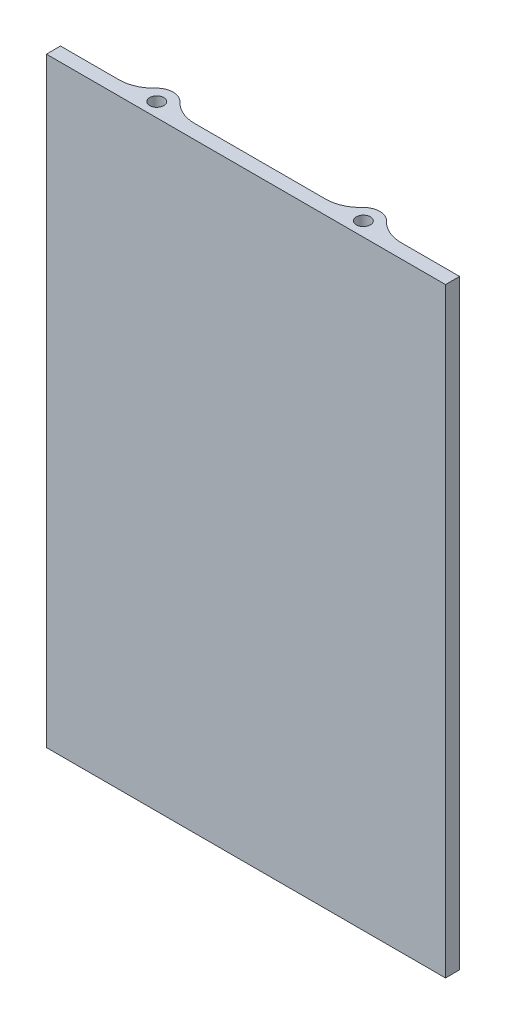
SolidWorks part; units mm, degrees
material "PLA"
ref_plane "Front Plane" through (0, 0, 0) normal (0, 0, 1) x (1, 0, 0)
ref_plane "Top Plane" through (0, 0, 0) normal (0, 1, 0) x (1, 0, 0)
ref_plane "Right Plane" through (0, 0, 0) normal (1, 0, 0) x (0, 0, -1)
other "Center of Mass"
sketch "Sketch1" plane through (0, 0, 0) normal (0, 1, 0) x (1, 0, 0)
  line L4 (-85, 6) -> (-85, 0)
  line L6 (-85, 0) -> (85, 0)
  line L7 (85, 6) -> (85, 0)
  line L8 (-85, 6) -> (85, 0) construction
  line L9 (-85, 0) -> (85, 6) construction
  line L14 (-85, 6) -> (-60.0935, 6)
  line L15 (0, 0) -> (0, 6) construction
  line L16 (-27.9065, 6) -> (27.9065, 6)
  line L18 (60.0935, 6) -> (85, 6)
  circle A0 centre (-44, 6) radius 3
  arc A12 (-60.0935, 6) -> (-49.1207, 10.7727) centre (-60.0935, 21) ccw
  arc A13 (-38.8793, 10.7727) -> (-27.9065, 6) centre (-27.9065, 21) ccw
  arc A14 (-38.8793, 10.7727) -> (-49.1207, 10.7727) centre (-44, 6) ccw
  arc A15 (38.8793, 10.7727) -> (49.1207, 10.7727) centre (44, 6) cw
  arc A16 (38.8793, 10.7727) -> (27.9065, 6) centre (27.9065, 21) cw
  arc A17 (60.0935, 6) -> (49.1207, 10.7727) centre (60.0935, 21) cw
  circle A18 centre (44, 6) radius 3
  point P1 (0, 3)
  dimension "D3" = 44
  dimension "D1" = 6
  dimension "D2" = 170
extrude "Boss-Extrude1" add sketch "Sketch1" along normal blind 255.8
